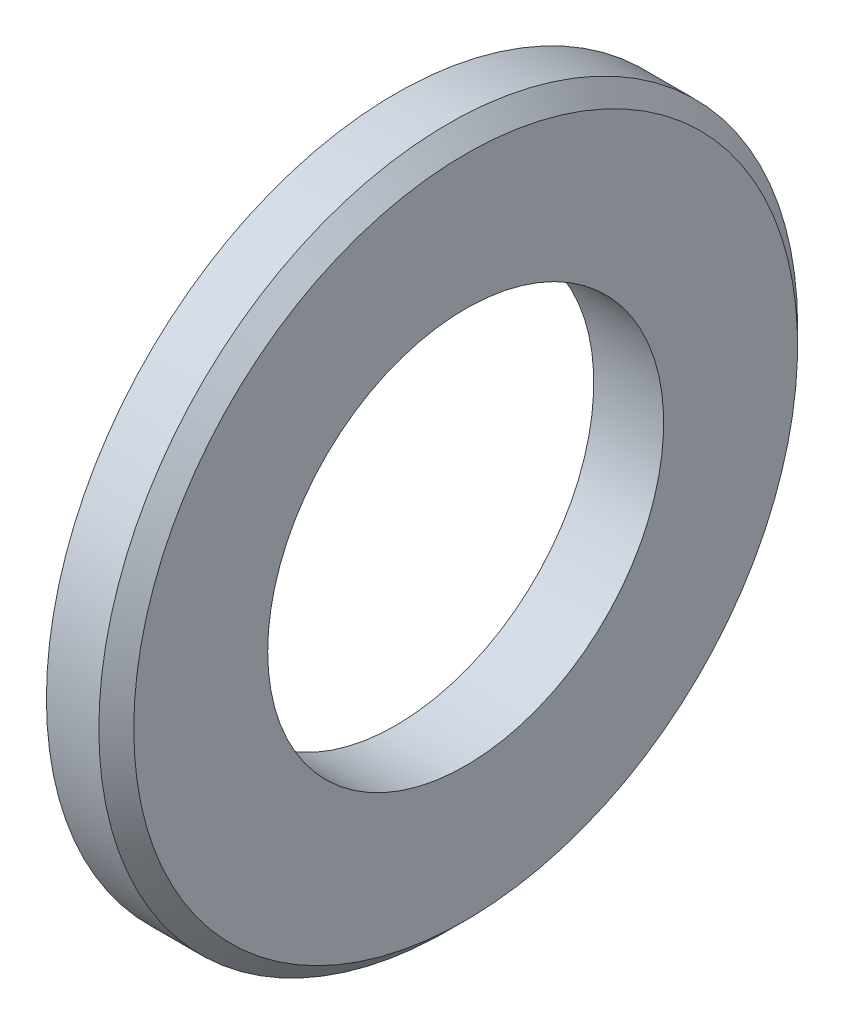
SolidWorks part; units mm, degrees
ref_plane "Plane1" through (0, 0, 0) normal (0, 0, 1) x (1, 0, 0)
ref_plane "Plane2" through (0, 0, 0) normal (0, 1, 0) x (1, 0, 0)
ref_plane "Plane3" through (0, 0, 0) normal (1, 0, 0) x (0, 0, -1)
sketch "Sketch1" plane through (0, 0, 0) normal (0, 0, 1) x (1, 0, 0)
  line L0 (-34.925, 0) -> (9.525, 0) construction
  line L1 (0, 8.5) -> (0, 15)
  line L2 (0, 15) -> (-3, 15)
  line L3 (-3, 15) -> (-3, 8.5)
  line L4 (-3, 8.5) -> (0, 8.5)
  dimension "Thickness" = 3
revolve "Base-Revolve" add sketch "Sketch1" angle 360 about L0
chamfer "ODChamfer" distance 0.75 angle 45 1 edges at (0, 0, 15)
equation "\"D1@ODChamfer\" =  \"Thickness@Sketch1\" * 0.25"
